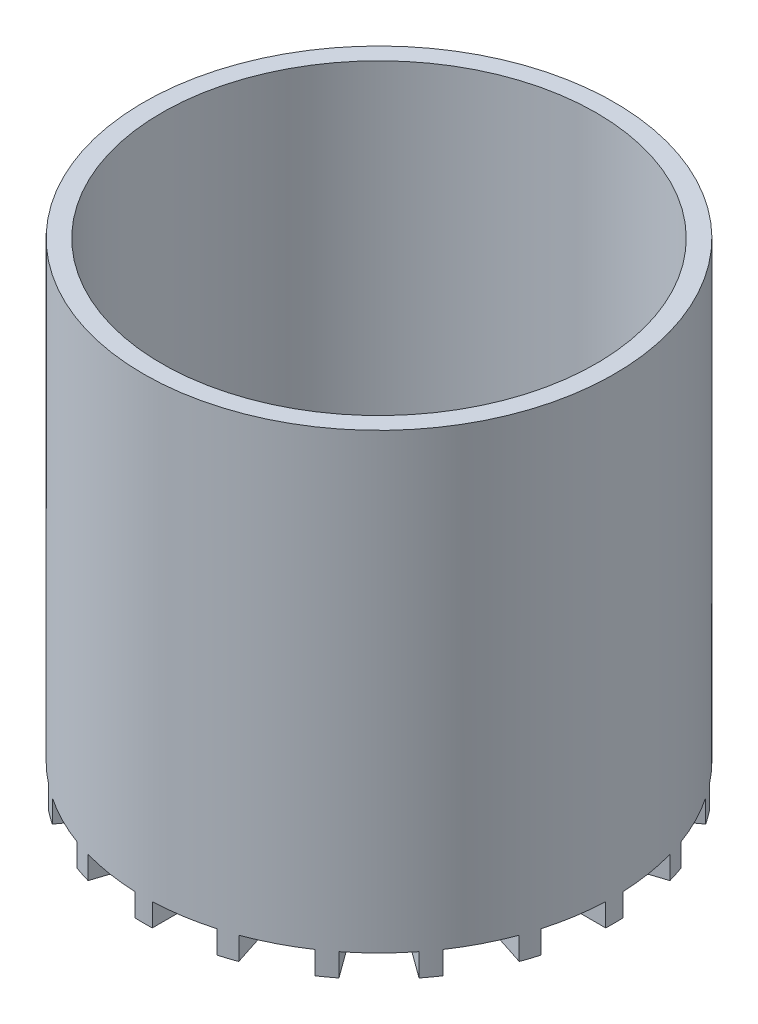
SolidWorks part; units mm, degrees
ref_plane "Front Plane" through (0, 0, 0) normal (0, 0, 1) x (1, 0, 0)
ref_plane "Top Plane" through (0, 0, 0) normal (0, 1, 0) x (1, 0, 0)
ref_plane "Right Plane" through (0, 0, 0) normal (1, 0, 0) x (0, 0, -1)
sketch "Sketch1" plane through (0, 0, 0) normal (0, 1, 0) x (1, 0, 0)
  circle A0 centre (0, 0) radius 38.1
  dimension "D1" = 76.2
extrude "Boss-Extrude1" add sketch "Sketch1" along normal blind 76.2
shell "Shell2" thickness 3.175 removed face at (0, 76.2, 38.1) outward yes
ref_axis "Axis1" through (0, 76.2, 0) along (0, -1, 0)
sketch "Sketch2" plane through (0, -3.175, 0) normal (0, -1, 0) x (-1, 0, 0)
  line L0 (0, 0) -> (0, 41.275)
  line L1 (-1.5, -41.275) -> (-1.5, 41.275)
  line L2 (-1.5, -41.275) -> (1.5, -41.275)
  line L3 (-1.5, 41.275) -> (1.5, 41.275)
  line L4 (1.5, -41.275) -> (1.5, 41.275)
  line L5 (-1.5, -41.275) -> (1.5, 41.275) construction
  line L6 (-1.5, 41.275) -> (1.5, -41.275) construction
  line L7 (-23.0473, -34.2739) -> (25.4744, 32.5105)
  line L8 (-25.4744, -32.5105) -> (23.0473, 34.2739)
  line L9 (-25.4744, -32.5105) -> (-23.0473, -34.2739)
  line L10 (23.0473, 34.2739) -> (25.4744, 32.5105)
  line L11 (-38.7913, -14.1813) -> (39.7184, 11.3281)
  line L12 (-39.7184, -11.3281) -> (38.7913, 14.1813)
  line L13 (-39.7184, -11.3281) -> (-38.7913, -14.1813)
  line L14 (38.7913, 14.1813) -> (39.7184, 11.3281)
  line L15 (-39.7184, 11.3281) -> (38.7913, -14.1813)
  line L16 (-38.7913, 14.1813) -> (39.7184, -11.3281)
  line L17 (-38.7913, 14.1813) -> (-39.7184, 11.3281)
  line L18 (39.7184, -11.3281) -> (38.7913, -14.1813)
  line L19 (-25.4744, 32.5105) -> (23.0473, -34.2739)
  line L20 (-23.0473, 34.2739) -> (25.4744, -32.5105)
  line L21 (-23.0473, 34.2739) -> (-25.4744, 32.5105)
  line L22 (25.4744, -32.5105) -> (23.0473, -34.2739)
  line L23 (-1.5, 41.275) -> (-1.5, -41.275)
  line L24 (1.5, 41.275) -> (1.5, -41.275)
  line L25 (1.5, 41.275) -> (-1.5, 41.275)
  line L26 (1.5, -41.275) -> (-1.5, -41.275)
  line L27 (-14.1813, 38.7913) -> (11.3281, -39.7184)
  line L28 (14.1813, -38.7913) -> (11.3281, -39.7184)
  line L29 (-11.3281, 39.7184) -> (14.1813, -38.7913)
  line L30 (-11.3281, 39.7184) -> (-14.1813, 38.7913)
  line L31 (11.3281, 39.7184) -> (-14.1813, -38.7913)
  line L32 (-11.3281, -39.7184) -> (-14.1813, -38.7913)
  line L33 (14.1813, 38.7913) -> (-11.3281, -39.7184)
  line L34 (14.1813, 38.7913) -> (11.3281, 39.7184)
  line L35 (32.5105, 25.4744) -> (-34.2739, -23.0473)
  line L36 (-32.5105, -25.4744) -> (-34.2739, -23.0473)
  line L37 (34.2739, 23.0473) -> (-32.5105, -25.4744)
  line L38 (34.2739, 23.0473) -> (32.5105, 25.4744)
  line L39 (-41.275, 1.5) -> (41.275, 1.5)
  line L40 (-41.275, 1.5) -> (-41.275, -1.5)
  line L41 (-41.275, -1.5) -> (41.275, -1.5)
  line L42 (41.275, 1.5) -> (41.275, -1.5)
  line L43 (-34.2739, 23.0473) -> (32.5105, -25.4744)
  line L44 (34.2739, -23.0473) -> (32.5105, -25.4744)
  line L45 (-32.5105, 25.4744) -> (34.2739, -23.0473)
  line L46 (-32.5105, 25.4744) -> (-34.2739, 23.0473)
  line L47 (38.7913, 14.1813) -> (-39.7184, -11.3281)
  line L48 (-38.7913, -14.1813) -> (-39.7184, -11.3281)
  line L49 (39.7184, 11.3281) -> (-38.7913, -14.1813)
  line L50 (39.7184, 11.3281) -> (38.7913, 14.1813)
  line L51 (39.7184, -11.3281) -> (-38.7913, 14.1813)
  line L52 (-39.7184, 11.3281) -> (-38.7913, 14.1813)
  line L53 (38.7913, -14.1813) -> (-39.7184, 11.3281)
  line L54 (38.7913, -14.1813) -> (39.7184, -11.3281)
  line L55 (25.4744, -32.5105) -> (-23.0473, 34.2739)
  line L56 (-25.4744, 32.5105) -> (-23.0473, 34.2739)
  line L57 (23.0473, -34.2739) -> (-25.4744, 32.5105)
  line L58 (23.0473, -34.2739) -> (25.4744, -32.5105)
  line L59 (1.5, 41.275) -> (1.5, -41.275)
  line L60 (1.5, 41.275) -> (-1.5, 41.275)
  line L61 (-1.5, 41.275) -> (-1.5, -41.275)
  line L62 (1.5, -41.275) -> (-1.5, -41.275)
  line L63 (23.0473, 34.2739) -> (-25.4744, -32.5105)
  line L64 (-23.0473, -34.2739) -> (-25.4744, -32.5105)
  line L65 (25.4744, 32.5105) -> (-23.0473, -34.2739)
  line L66 (25.4744, 32.5105) -> (23.0473, 34.2739)
  line L67 (14.1813, -38.7913) -> (-11.3281, 39.7184)
  line L68 (-14.1813, 38.7913) -> (-11.3281, 39.7184)
  line L69 (11.3281, -39.7184) -> (-14.1813, 38.7913)
  line L70 (11.3281, -39.7184) -> (14.1813, -38.7913)
  line L71 (-11.3281, -39.7184) -> (14.1813, 38.7913)
  line L72 (11.3281, 39.7184) -> (14.1813, 38.7913)
  line L73 (-14.1813, -38.7913) -> (11.3281, 39.7184)
  line L74 (-14.1813, -38.7913) -> (-11.3281, -39.7184)
  line L75 (-32.5105, -25.4744) -> (34.2739, 23.0473)
  line L76 (32.5105, 25.4744) -> (34.2739, 23.0473)
  line L77 (-34.2739, -23.0473) -> (32.5105, 25.4744)
  line L78 (-34.2739, -23.0473) -> (-32.5105, -25.4744)
  line L79 (41.275, -1.5) -> (-41.275, -1.5)
  line L80 (41.275, -1.5) -> (41.275, 1.5)
  line L81 (41.275, 1.5) -> (-41.275, 1.5)
  line L82 (-41.275, -1.5) -> (-41.275, 1.5)
  line L83 (34.2739, -23.0473) -> (-32.5105, 25.4744)
  line L84 (-34.2739, 23.0473) -> (-32.5105, 25.4744)
  line L85 (32.5105, -25.4744) -> (-34.2739, 23.0473)
  line L86 (32.5105, -25.4744) -> (34.2739, -23.0473)
  circle A1 centre (0, 0) radius 41.275 construction
  circle A2 centre (0, 0) radius 41.275
  dimension "D1" = 3
  dimension "D2" = 6
  dimension "D3" = 4
extrude "Boss-Extrude2" add sketch "Sketch2" along normal blind 4 contours L4 L3 L1 L2 | L7 L10 L8 L9 | L11 L14 L12 L13 | L15 L18 L16 L17 | L20 L22 L19 L21 | L35 L36 L37 L38 | L39 L42 L41 L40 | L43 L44 L45 L46 | L27 L28 L29 L30 | L31 L32 L33 L34
sketch "Sketch3" plane through (0, -3.175, 0) normal (0, -1, 0) x (1, 0, 0)
  circle A0 centre (0, 0) radius 41.275
  circle A1 centre (0, 0) radius 61.9063
extrude "Cut-Extrude1" cut sketch "Sketch3" against normal through all both and the other way through all
sketch "Sketch4" plane through (0, -7.175, 0) normal (0, -1, 0) x (1, 0, 0)
  circle A0 centre (0, 0) radius 20.64
extrude "Cut-Extrude2" cut sketch "Sketch4" against normal blind 4
